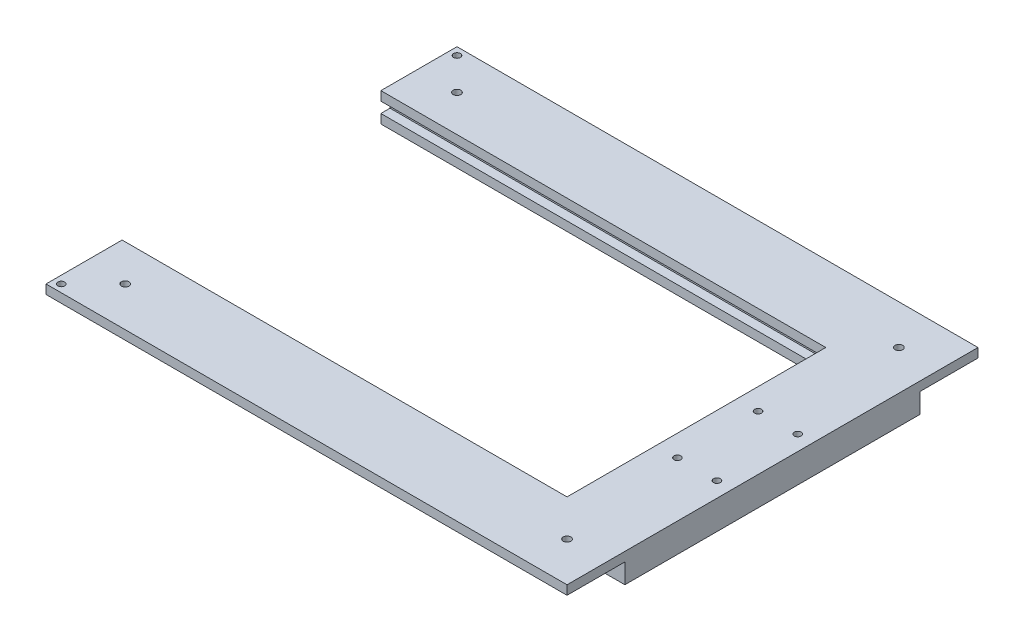
SolidWorks part; units mm, degrees
ref_plane "Спереди" through (0, 0, 0) normal (0, 0, 1) x (1, 0, 0)
ref_plane "Сверху" through (0, 0, 0) normal (0, 1, 0) x (1, 0, 0)
ref_plane "Справа" through (0, 0, 0) normal (1, 0, 0) x (0, 0, -1)
sketch "Эскиз1" plane through (0, 0, 0) normal (0, 1, 0) x (1, 0, 0)
  line L0 (50, -77.9215) -> (50, -347.9215)
  line L1 (-292.3, -77.9215) -> (50, -77.9215)
  line L2 (-292.3, -77.9215) -> (-292.3, -127.9215)
  line L3 (-292.3, -347.9215) -> (50, -347.9215)
  line L5 (-292.3, -127.9215) -> (0, -127.9215)
  line L7 (-292.3, -297.9215) -> (0, -297.9215)
  line L13 (-292.3, -297.9215) -> (-292.3, -347.9215)
  line L22 (0, -127.9215) -> (0, -297.9215)
  dimension "D1" = 342.3
  dimension "D12" = 50
  dimension "D2" = 270
  dimension "D3" = 50
  dimension "D4" = 50
  dimension "D9" = 50
  dimension "D8" = 77.9215
extrude "Бобышка-Вытянуть2" add sketch "Эскиз1" along normal blind 6
sketch "Эскиз2" plane through (0, 0, 0) normal (0, -1, 0) x (1, 0, 0)
  line L0 (-292.3, 127.9215) -> (0, 127.9215) construction
  line L5 (50, 347.9215) -> (50, 77.9215) construction
  line L6 (0, 297.9215) -> (-292.3, 297.9215) construction
  line L18 (50, 309.9215) -> (50, 115.9215)
  line L20 (6, 303.9215) -> (6, 121.9215)
  line L21 (-292.3, 77.9215) -> (-292.3, 127.9215) construction
  line L22 (50, 115.9215) -> (-292.3, 115.9215)
  line L24 (6, 121.9215) -> (-292.3, 121.9215)
  line L25 (-292.3, 115.9215) -> (-292.3, 121.9215)
  line L26 (-292.3, 297.9215) -> (-292.3, 347.9215) construction
  line L27 (50, 309.9215) -> (-292.3, 309.9215)
  line L29 (6, 303.9215) -> (-292.3, 303.9215)
  line L30 (-292.3, 309.9215) -> (-292.3, 303.9215)
  dimension "D1" = 44
  dimension "D2" = 6
  dimension "D3" = 6
  dimension "D4" = 6
  dimension "D5" = 6
extrude "Бобышка-Вытянуть3" add sketch "Эскиз2" along normal blind 7
sketch "Эскиз4" plane through (0, 6, 0) normal (0, 1, 0) x (1, 0, 0)
  line L0 (50, -77.9215) -> (-292.3, -77.9215) construction
  line L1 (-292.3, -77.9215) -> (-292.3, -127.9215) construction
  circle A0 centre (-266.3, -103.9215) radius 2.5
  dimension "D1" = 5
  dimension "D2" = 26
  dimension "D3" = 26
extrude "Вырез-Вытянуть1" cut sketch "Эскиз4" against normal through all
pattern_linear "Линейный массив2" count 2 spacing 290.3 along (1, 0, 0) count 2 spacing 218 along (0, 0, 1) of "Вырез-Вытянуть1"
sketch "Эскиз5" plane through (0, -7, 0) normal (0, -1, 0) x (1, 0, 0)
  line L8 (50, 309.9215) -> (-292.3, 309.9215)
  line L9 (-292.3, 309.9215) -> (-292.3, 297.9215)
  line L10 (-292.3, 297.9215) -> (0, 297.9215)
  line L11 (0, 297.9215) -> (0, 127.9215)
  line L12 (0, 127.9215) -> (-292.3, 127.9215)
  line L13 (-292.3, 127.9215) -> (-292.3, 115.9215)
  line L14 (-292.3, 115.9215) -> (50, 115.9215)
  line L15 (50, 115.9215) -> (50, 309.9215)
extrude "Бобышка-Вытянуть4" add sketch "Эскиз5" along normal blind 6
sketch "Эскиз6" plane through (0, -13, 0) normal (0, -1, 0) x (1, 0, 0)
  line L0 (40, 212.9215) -> (50, 212.9215) construction
  line L1 (40, 186.4215) -> (14, 186.4215) construction
  line L2 (40, 186.4215) -> (40, 239.4215) construction
  line L3 (40, 239.4215) -> (14, 239.4215) construction
  line L4 (14, 186.4215) -> (14, 239.4215) construction
  line L5 (50, 115.9215) -> (50, 309.9215) construction
  circle A1 centre (14, 239.4215) radius 2.25
  circle A2 centre (40, 239.4215) radius 2.25
  circle A3 centre (40, 186.4215) radius 2.25
  circle A4 centre (14, 186.4215) radius 2.25
  point P4 (50, 212.9215)
  point P6 (40, 212.9215)
  dimension "D4" = 4.5
  dimension "D1" = 53
  dimension "D2" = 26
  dimension "D3" = 10
extrude "Вырез-Вытянуть2" cut sketch "Эскиз6" against normal through all
sketch "Эскиз7" plane through (0, 0, 0) normal (0, -1, 0) x (1, 0, 0)
  line L0 (-292.3, 337.9215) -> (-282.3, 347.9215) construction
  line L1 (-292.3, 347.9215) -> (-282.3, 347.9215) construction
  line L2 (-292.3, 347.9215) -> (-292.3, 337.9215) construction
  line L3 (-292.3, 337.9215) -> (-282.3, 337.9215) construction
  line L4 (-282.3, 347.9215) -> (-282.3, 337.9215) construction
  line L5 (-292.3, 347.9215) -> (-282.3, 337.9215) construction
  line L6 (-282.3, 87.9215) -> (-292.3, 77.9215) construction
  line L7 (-292.3, 77.9215) -> (-282.3, 77.9215) construction
  line L8 (-292.3, 77.9215) -> (-292.3, 87.9215) construction
  line L9 (-292.3, 87.9215) -> (-282.3, 87.9215) construction
  line L10 (-282.3, 77.9215) -> (-282.3, 87.9215) construction
  line L11 (-292.3, 87.9215) -> (-282.3, 77.9215) construction
  circle A0 centre (-287.3, 342.9215) radius 2.25
  circle A1 centre (-287.3, 82.9215) radius 2.25
  point P12 (-287.3, 82.9215)
  dimension "D3" = 4.5
  dimension "D6" = 4.5
  dimension "D1" = 10
  dimension "D2" = 10
  dimension "D4" = 10
  dimension "D5" = 10
extrude "Вырез-Вытянуть3" cut sketch "Эскиз7" against normal through all
equation "\"Ширина груза\"= 160"
equation "\"Глубина груза\"= 240"
equation "\"Высота груза\"= 160"
equation "\"Ширина ячейки\"= \"Ширина груза\" + 10"
equation "\"Глубина ячейки\"= \"Глубина груза\" + 10"
equation "\"Высота ячейки\"= \"Высота груза\" + 10 + 13"
equation "\"Колво ячеек ширина\"= 2"
equation "\"Колво ячеек высота\"= 2"
equation "\"Толщина стенки\" = \"Толщина тонких панелей\""
equation "\"Крепление дверцы\"= 5 "
equation "\"Ширина рейки\"= \"Толщина шестерни\""
equation "\"Высота рейки\"= 20"
equation "\"Высота пола\" = 2*\"Толщина тонких панелей\""
equation "\"Колво полозьев\"= 5"
equation "\"Отступ рейки\"= 20"
equation "\"Глубина каретки\"= \"Глубина ячейки\" + 30 + \"Мотор Y высота корпуса\" + 20"
equation "\"Длинна рейки\" = (\"Ширина ячейки\"+\"Толщина вертикальных стенок\"+\"Крепление дверцы\")*\"Колво ячеек ширина\"+\"Ширина ячейки выгрузки\"*\"Колво выгрузки\"+\"Толщина вертикальных стенок\"+2*\"Отступ крепления мотора фиксации\"-\"Крепление дверцы\"*\"Колво ячеек ширина\""
equation "\"Отступ шпильки\"= 26"
equation "\"Диаметр шпильки\"= 5"
equation "\"Длинна шпильки\" = (\"Высота ячейки\"+\"Толщина горизонтальных плит\"+\"Высота пола\")*\"Колво ячеек высота\"+2*(\"Толщина горизонтальных плит\"+\"Отступ рейки\")"
equation "\"D2@Эскиз1\"=\"Ширина ячейки\" + \"Ширина пластины\" * 2 "
equation "\"D9@Эскиз1\"=\"Ширина пластины\""
equation "\"D3@Эскиз1\"=\"Ширина пластины\""
equation "\"D4@Эскиз1\"= \"Ширина пластины\""
equation "\"Ширина пластины\"= 50  "
equation "\"D1@Бобышка-Вытянуть2\"=\"Толщина стенки\""
equation "\"D1@Эскиз4\"= \"Диаметр шпильки\""
equation "\"D4@Линейный массив2\"=\"Ширина ячейки\" + \"Ширина пластины\" * 2  - \"Отступ шпильки\" * 2"
equation "\"D1@Эскиз1\"= \"Глубина каретки\""
equation "\"D3@Линейный массив2\"= \"Глубина каретки\" - \"Отступ шпильки\" * 2"
equation "\"D2@Эскиз4\"=\"Отступ шпильки\""
equation "\"D3@Эскиз4\"= \"Отступ шпильки\""
equation "\"D1@Эскиз2\"= \"Ширина пластины\" - \"Толщина стенки\""
equation "\"D2@Эскиз2\"= \"Толщина стенки\""
equation "\"D3@Эскиз2\"= \"Толщина стенки\""
equation "\"D4@Эскиз2\"= \"Толщина стенки\""
equation "\"D5@Эскиз2\"= \"Толщина стенки\""
equation "\"D1@Бобышка-Вытянуть4\"= \"Толщина стенки\""
equation "\"Вы\"=20"
equation "\"D1@Бобышка-Вытянуть3\"=\"Высота пола\" - 5"
equation "\"Высота зона выгрузки\"= \"Высота ячейки\" * 2 + \"Толщина стенки\" * 2"
equation "\"Колво выгрузки\"= 1"
equation "\"Ширина ячейки выгрузки\" = \"Ширина ячейки\"+\"Толщина вертикальных стенок\"+2*\"Отступ крепления мотора фиксации\""
equation "\"Отступ крепления мотора фиксации\" = (\"Ширина пластины\"+20-\"Толщина вертикальных стенок\")/2"
equation "\"Мотор X ширина корпуса\"= 42.3"
equation "\"Мотор X высота корпуса\"= 42.3"
equation "\"Мотор X длина корпуса\"= 40"
equation "\"Мотор X вылет вала\"= 19.8"
equation "\"Мотор Y ширина корпуса\"= 42.3"
equation "\"Мотор Y высота корпуса\"= 42.3"
equation "\"Мотор Y длина корпуса\"= 48"
equation "\"Мотор Y вылет вала\"= 30"
equation "\"Мотор Z ширина корпуса\"= 42"
equation "\"Мотор Z высота корпуса\"= 42"
equation "\"Мотор Z длина корпуса\"= 40"
equation "\"Мотор Z вылет вала\"= 23"
equation "\"Мотор диаметр вала ПРЕДВ\"= 5"
equation "\"Мотор шаг крепления ПРЕДВ\"= 31"
equation "\"Мотор диаметр отверстий ПРЕДВ\"= 3"
equation "\"Мотор глубина отверстий ПРЕДВ\"= 4.5"
equation "\"Мотор диаметр буртика ПРЕДВ\"= 22"
equation "\"Мотор высота буртика ПРЕДВ\"= 2"
equation "\"Мотор диаметр шкива ПРЕДВ\"= 16"
equation "\"Мотор длина шкива ПРЕДВ\"= 12"
equation "\"Мотор отступ шкива ПРЕДВ\"= 5"
equation "\"Мотор X шаг градусов\"= 1.8"
equation "\"Мотор X ток А\"= 1.5"
equation "\"Мотор X сопротивление Ом\"= 1.3"
equation "\"Мотор X индуктивность мГн\"= 2"
equation "\"Мотор Y шаг градусов\"= 1.8"
equation "\"Мотор Y ток А\"= 2.2"
equation "\"Мотор Y сопротивление Ом\"= 0.9"
equation "\"Мотор Y индуктивность мГн\"= 2"
equation "\"Мотор Z шаг градусов\"= 1.8"
equation "\"Мотор Z ток А\"= 1"
equation "\"Мотор Z сопротивление Ом\"= 4"
equation "\"Мотор Z индуктивность мГн\"= 8"
equation "\"Мотор Y диаметр ротора\"= 25.78"
equation "\"Толщина тонких панелей\" = 6"
equation "\"Толщина вертикальных стенок\" = 6"
equation "\"Толщина горизонтальных плит\" = 6"
equation "\"Базовая высота корпуса\"= (\"Высота ячейки\"+\"Толщина тонких панелей\"+\"Высота пола\")*\"Колво ячеек высота\"+6*\"Толщина тонких панелей\"+\"Мотор X ширина корпуса\"+\"Мотор Y ширина корпуса\"+75"
equation "\"Высота корпуса\"= (\"Высота ячейки\"+\"Толщина горизонтальных плит\"+\"Высота пола\")*\"Колво ячеек высота\"+2*\"Толщина горизонтальных плит\"+4*\"Толщина тонких панелей\"+\"Мотор X ширина корпуса\"+\"Мотор Y ширина корпуса\"+75"
equation "\"Смещение центра корпуса\"= (\"Высота корпуса\"-\"Базовая высота корпуса\")/2-(\"Толщина горизонтальных плит\"-\"Толщина тонких панелей\")"
equation "\"Отметка пола\"= -\"Базовая высота корпуса\"/2+\"Толщина тонких панелей\""
equation "\"Отметка потолка\"= \"Отметка пола\"+\"Высота корпуса\"-2*\"Толщина горизонтальных плит\""
equation "\"Отметка верхней полки\"= \"Отметка потолка\"-(28+\"Толщина тонких панелей\")-\"Высота ячейки\"-\"Высота пола\""
equation "\"Отметка нижней полки\"= \"Отметка верхней полки\"-\"Высота ячейки\"-\"Высота пола\"-\"Толщина горизонтальных плит\""
equation "\"Толщина шестерни\"= 10"
